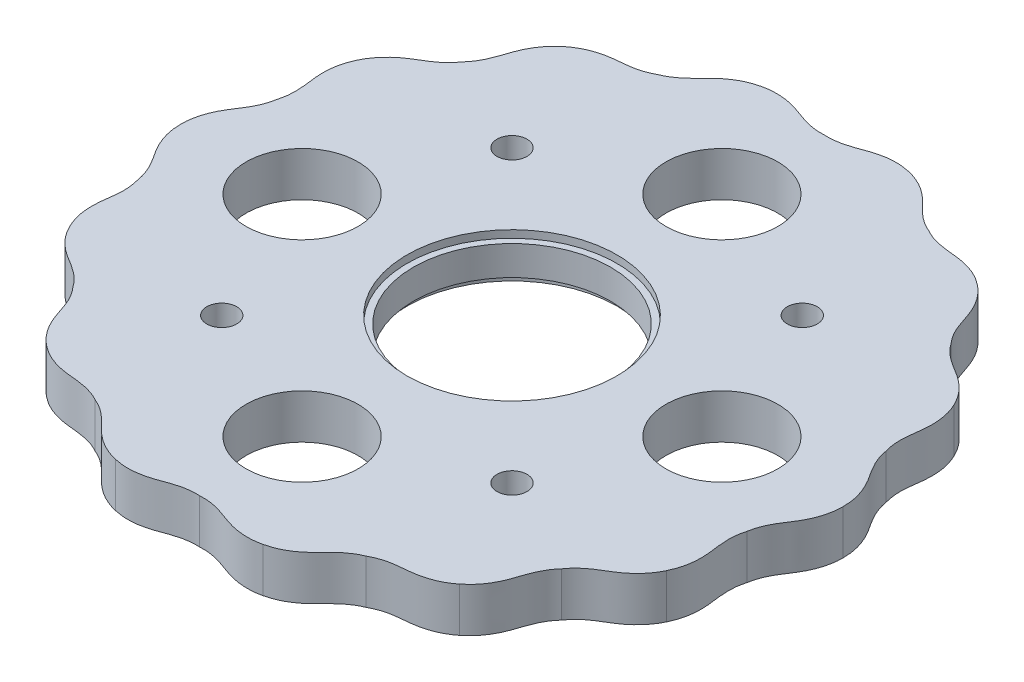
SolidWorks part; units mm, degrees
ref_plane "Front Plane" through (0, 0, 0) normal (0, 0, 1) x (1, 0, 0)
ref_plane "Top Plane" through (0, 0, 0) normal (0, 1, 0) x (1, 0, 0)
ref_plane "Right Plane" through (0, 0, 0) normal (1, 0, 0) x (0, 0, -1)
sketch "Sketch1" plane through (0, 0, 0) normal (0, 1, 0) x (1, 0, 0)
  line L0 (0, 0) -> (37.5, 0) construction
  line L1 (0, 0) -> (37.4807, 1.2019) construction
  line L2 (0, 0) -> (37.423, 2.4026) construction
  line L3 (0, 0) -> (37.3267, 3.6009) construction
  line L4 (0, 0) -> (37.1921, 4.7954) construction
  line L5 (0, 0) -> (37.0193, 5.985) construction
  line L6 (0, 0) -> (36.8085, 7.1684) construction
  line L7 (0, 0) -> (36.5598, 8.3445) construction
  line L8 (0, 0) -> (36.2736, 9.512) construction
  line L9 (0, 0) -> (35.95, 10.6698) construction
  line L10 (0, 0) -> (35.5896, 11.8166) construction
  line L11 (0, 0) -> (35.1926, 12.9512) construction
  line L12 (0, 0) -> (34.7594, 14.0725) construction
  line L13 (0, 0) -> (34.2905, 15.1794) construction
  line L14 (0, 0) -> (33.7863, 16.2706) construction
  line L15 (37.5, 0) -> (38.5, 0) construction
  line L16 (37.4807, 1.2019) -> (38.3521, 1.6927) construction
  line L17 (37.423, 2.4026) -> (37.9413, 3.2578) construction
  line L18 (37.3267, 3.6009) -> (37.3588, 4.6003) construction
  line L19 (37.1921, 4.7954) -> (36.7296, 5.682) construction
  line L20 (37.0193, 5.985) -> (36.1812, 6.5305) construction
  line L21 (36.8085, 7.1684) -> (35.8105, 7.2325) construction
  line L22 (36.5598, 8.3445) -> (35.5849, 8.122) construction
  line L23 (37, 0.0019) -> (37, 0)
  line L24 (33.3367, 16.052) -> (33.3358, 16.0537)
  line L25 (37, -0.0019) -> (37, 0)
  line L26 (33.3367, -16.052) -> (33.3358, -16.0537)
  line L27 (33.335, -16.0554) -> (33.3358, -16.0537)
  line L28 (23.0706, -28.9266) -> (23.0691, -28.9278)
  line L29 (23.0677, -28.9289) -> (23.0691, -28.9278)
  line L30 (8.2351, -36.0719) -> (8.2333, -36.0723)
  line L31 (8.2315, -36.0727) -> (8.2333, -36.0723)
  line L32 (-8.2315, -36.0727) -> (-8.2333, -36.0723)
  line L33 (-8.2351, -36.0719) -> (-8.2333, -36.0723)
  line L34 (-23.0677, -28.9289) -> (-23.0691, -28.9278)
  line L35 (-23.0706, -28.9266) -> (-23.0691, -28.9278)
  line L36 (-33.335, -16.0554) -> (-33.3358, -16.0537)
  line L37 (-33.3367, -16.052) -> (-33.3358, -16.0537)
  line L38 (-37, -0.0019) -> (-37, 0)
  line L39 (-37, 0.0019) -> (-37, 0)
  line L40 (-33.3367, 16.052) -> (-33.3358, 16.0537)
  line L41 (-33.335, 16.0554) -> (-33.3358, 16.0537)
  line L42 (-23.0706, 28.9266) -> (-23.0691, 28.9278)
  line L43 (-23.0677, 28.9289) -> (-23.0691, 28.9278)
  line L44 (-8.2351, 36.0719) -> (-8.2333, 36.0723)
  line L45 (-8.2315, 36.0727) -> (-8.2333, 36.0723)
  line L46 (8.2315, 36.0727) -> (8.2333, 36.0723)
  line L47 (8.2351, 36.0719) -> (8.2333, 36.0723)
  line L48 (23.0677, 28.9289) -> (23.0691, 28.9278)
  line L49 (23.0706, 28.9266) -> (23.0691, 28.9278)
  line L50 (33.335, 16.0554) -> (33.3358, 16.0537)
  line L51 (35.5, 0.0037) -> (35.5, 0)
  line L52 (31.986, 15.3995) -> (31.9844, 15.4029)
  line L53 (35.5, -0.0037) -> (35.5, 0)
  line L54 (31.986, -15.3995) -> (31.9844, -15.4029)
  line L55 (31.9828, -15.4062) -> (31.9844, -15.4029)
  line L56 (22.1368, -27.7527) -> (22.1339, -27.755)
  line L57 (22.131, -27.7573) -> (22.1339, -27.755)
  line L58 (7.9031, -34.6091) -> (7.8995, -34.6099)
  line L59 (7.8959, -34.6108) -> (7.8995, -34.6099)
  line L60 (-7.8959, -34.6108) -> (-7.8995, -34.6099)
  line L61 (-7.9031, -34.6091) -> (-7.8995, -34.6099)
  line L62 (-22.131, -27.7573) -> (-22.1339, -27.755)
  line L63 (-22.1368, -27.7527) -> (-22.1339, -27.755)
  line L64 (-31.9828, -15.4062) -> (-31.9844, -15.4029)
  line L65 (-31.986, -15.3995) -> (-31.9844, -15.4029)
  line L66 (-35.5, -0.0037) -> (-35.5, 0)
  line L67 (-35.5, 0.0037) -> (-35.5, 0)
  line L68 (-31.986, 15.3995) -> (-31.9844, 15.4029)
  line L69 (-31.9828, 15.4062) -> (-31.9844, 15.4029)
  line L70 (-22.1368, 27.7527) -> (-22.1339, 27.755)
  line L71 (-22.131, 27.7573) -> (-22.1339, 27.755)
  line L72 (-7.9031, 34.6091) -> (-7.8995, 34.6099)
  line L73 (-7.8959, 34.6108) -> (-7.8995, 34.6099)
  line L74 (7.8959, 34.6108) -> (7.8995, 34.6099)
  line L75 (7.9031, 34.6091) -> (7.8995, 34.6099)
  line L76 (22.131, 27.7573) -> (22.1339, 27.755)
  line L77 (22.1368, 27.7527) -> (22.1339, 27.755)
  line L78 (31.9828, 15.4062) -> (31.9844, 15.4029)
  circle A0 centre (0, 0) radius 35 construction
  circle A1 centre (37.5, 0) radius 2.5 construction
  circle A2 centre (0, 0) radius 37.5 construction
  spline S0 degree 3 poles (35.5849, 8.122) (35.6266, 7.5364) (36.0345, 6.7125) (36.7836, 5.6218) (37.4152, 4.5501) (38.2239, 2.702) (38.5014, 1.1074) (38.5, 0) knots 0 0 0 0 0.195516 0.310928 0.453873 0.621058 1 1 1 1
  spline S1 degree 3 poles (35.5849, 8.122) (35.3683, 8.6678) (35.3784, 9.5871) (35.5801, 10.8948) (35.6841, 12.1344) (35.611, 14.1503) (35.169, 15.7074) (34.6873, 16.7045) knots 0 0 0 0 0.195516 0.310928 0.453873 0.621058 1 1 1 1
  spline S2 degree 1 poles (34.1119, 7.7858) (33.3367, 16.052) knots 0 0 1 1 construction
  spline S3 degree 1 poles (34.1119, 7.7858) (37, 0.0019) knots 0 0 1 1 construction
  spline S4 degree 3 poles (33.3367, 16.052) (33.6005, 15.5058) (33.9037, 14.6401) (34.1146, 13.4372) (34.174, 12.5211) (34.1413, 11.5771) (34.0239, 10.6392) (33.8823, 9.6155) (33.9055, 8.625) (34.0243, 8.0514) (34.1119, 7.7858) knots 0.015853 0.015853 0.015853 0.015853 0.26189 0.384908 0.507927 0.630945 0.753963 0.876982 0.938491 1 1 1 1
  spline S5 degree 3 poles (34.1119, 7.7858) (34.1483, 7.5085) (34.2901, 6.9402) (34.6989, 6.0377) (35.2706, 5.1769) (35.7834, 4.3828) (36.2224, 3.5464) (36.5664, 2.6953) (36.8983, 1.52) (37.0008, 0.6085) (37, 0.0019) knots 0.015853 0.015853 0.015853 0.015853 0.077362 0.138872 0.26189 0.384908 0.507927 0.630945 0.753963 1 1 1 1
  spline S6 degree 3 poles (37, -0.0019) (37.0008, -0.6085) (36.8983, -1.52) (36.5664, -2.6953) (36.2224, -3.5464) (35.7834, -4.3828) (35.2706, -5.1769) (34.6989, -6.0377) (34.2901, -6.9402) (34.1483, -7.5085) (34.1119, -7.7858) knots 0.015853 0.015853 0.015853 0.015853 0.26189 0.384908 0.507927 0.630945 0.753963 0.876982 0.938491 1 1 1 1
  spline S7 degree 3 poles (34.1119, -7.7858) (34.0243, -8.0514) (33.9055, -8.625) (33.8823, -9.6155) (34.0239, -10.6392) (34.1413, -11.5771) (34.174, -12.5211) (34.1146, -13.4372) (33.9037, -14.6401) (33.6005, -15.5058) (33.3367, -16.052) knots 0.015853 0.015853 0.015853 0.015853 0.077362 0.138872 0.26189 0.384908 0.507927 0.630945 0.753963 1 1 1 1
  spline S8 degree 3 poles (33.335, -16.0554) (33.0725, -16.6022) (32.5847, -17.3791) (31.7758, -18.2939) (31.0965, -18.9115) (30.3381, -19.4746) (29.5316, -19.9675) (28.6429, -20.4951) (27.8831, -21.1308) (27.5087, -21.5813) (27.3556, -21.8154) knots 0.015853 0.015853 0.015853 0.015853 0.26189 0.384908 0.507927 0.630945 0.753963 0.876982 0.938491 1 1 1 1
  spline S9 degree 3 poles (27.3556, -21.8154) (27.1615, -22.0167) (26.8056, -22.4819) (26.3549, -23.3642) (26.0383, -24.348) (25.7371, -25.2439) (25.357, -26.1087) (24.906, -26.9083) (24.1941, -27.9005) (23.5453, -28.549) (23.0706, -28.9266) knots 0.015853 0.015853 0.015853 0.015853 0.077362 0.138872 0.26189 0.384908 0.507927 0.630945 0.753963 1 1 1 1
  spline S10 degree 3 poles (23.0677, -28.9289) (22.5939, -29.3077) (21.8173, -29.796) (20.6915, -30.2693) (19.8116, -30.531) (18.884, -30.7092) (17.9435, -30.8034) (16.9139, -30.8931) (15.9535, -31.1362) (15.4207, -31.3797) (15.1812, -31.5241) knots 0.015853 0.015853 0.015853 0.015853 0.26189 0.384908 0.507927 0.630945 0.753963 0.876982 0.938491 1 1 1 1
  spline S11 degree 3 poles (15.1812, -31.5241) (14.919, -31.6213) (14.3964, -31.886) (13.6076, -32.4854) (12.8955, -33.2344) (12.2354, -33.9109) (11.5177, -34.5251) (10.7645, -35.0499) (9.6926, -35.6349) (8.8266, -35.9377) (8.2351, -36.0719) knots 0.015853 0.015853 0.015853 0.015853 0.077362 0.138872 0.26189 0.384908 0.507927 0.630945 0.753963 1 1 1 1
  spline S12 degree 3 poles (8.2315, -36.0727) (7.6402, -36.2085) (6.7287, -36.3114) (5.5091, -36.2494) (4.6028, -36.1034) (3.6897, -35.8614) (2.8014, -35.5383) (1.8349, -35.1724) (0.8641, -34.9747) (0.2785, -34.9629) (0, -34.9891) knots 0.015853 0.015853 0.015853 0.015853 0.26189 0.384908 0.507927 0.630945 0.753963 0.876982 0.938491 1 1 1 1
  spline S13 degree 3 poles (0, -34.9891) (-0.2785, -34.9629) (-0.8641, -34.9747) (-1.8349, -35.1724) (-2.8014, -35.5383) (-3.6897, -35.8614) (-4.6028, -36.1034) (-5.5091, -36.2494) (-6.7287, -36.3114) (-7.6402, -36.2085) (-8.2315, -36.0727) knots 0.015853 0.015853 0.015853 0.015853 0.077362 0.138872 0.26189 0.384908 0.507927 0.630945 0.753963 1 1 1 1
  spline S14 degree 3 poles (-8.2351, -36.0719) (-8.8266, -35.9377) (-9.6926, -35.6349) (-10.7645, -35.0499) (-11.5177, -34.5251) (-12.2354, -33.9109) (-12.8955, -33.2344) (-13.6076, -32.4854) (-14.3964, -31.886) (-14.919, -31.6213) (-15.1812, -31.5241) knots 0.015853 0.015853 0.015853 0.015853 0.26189 0.384908 0.507927 0.630945 0.753963 0.876982 0.938491 1 1 1 1
  spline S15 degree 3 poles (-15.1812, -31.5241) (-15.4207, -31.3797) (-15.9535, -31.1362) (-16.9139, -30.8931) (-17.9435, -30.8034) (-18.884, -30.7092) (-19.8116, -30.531) (-20.6915, -30.2693) (-21.8173, -29.796) (-22.5939, -29.3077) (-23.0677, -28.9289) knots 0.015853 0.015853 0.015853 0.015853 0.077362 0.138872 0.26189 0.384908 0.507927 0.630945 0.753963 1 1 1 1
  spline S16 degree 3 poles (-23.0706, -28.9266) (-23.5453, -28.549) (-24.1941, -27.9005) (-24.906, -26.9083) (-25.357, -26.1087) (-25.7371, -25.2439) (-26.0383, -24.348) (-26.3549, -23.3642) (-26.8056, -22.4819) (-27.1615, -22.0167) (-27.3556, -21.8154) knots 0.015853 0.015853 0.015853 0.015853 0.26189 0.384908 0.507927 0.630945 0.753963 0.876982 0.938491 1 1 1 1
  spline S17 degree 3 poles (-27.3556, -21.8154) (-27.5087, -21.5813) (-27.8831, -21.1308) (-28.6429, -20.4951) (-29.5316, -19.9675) (-30.3381, -19.4746) (-31.0965, -18.9115) (-31.7758, -18.2939) (-32.5847, -17.3791) (-33.0725, -16.6022) (-33.335, -16.0554) knots 0.015853 0.015853 0.015853 0.015853 0.077362 0.138872 0.26189 0.384908 0.507927 0.630945 0.753963 1 1 1 1
  spline S18 degree 3 poles (-33.3367, -16.052) (-33.6005, -15.5058) (-33.9037, -14.6401) (-34.1146, -13.4372) (-34.174, -12.5211) (-34.1413, -11.5771) (-34.0239, -10.6392) (-33.8823, -9.6155) (-33.9055, -8.625) (-34.0243, -8.0514) (-34.1119, -7.7858) knots 0.015853 0.015853 0.015853 0.015853 0.26189 0.384908 0.507927 0.630945 0.753963 0.876982 0.938491 1 1 1 1
  spline S19 degree 3 poles (-34.1119, -7.7858) (-34.1483, -7.5085) (-34.2901, -6.9402) (-34.6989, -6.0377) (-35.2706, -5.1769) (-35.7834, -4.3828) (-36.2224, -3.5464) (-36.5664, -2.6953) (-36.8983, -1.52) (-37.0008, -0.6085) (-37, -0.0019) knots 0.015853 0.015853 0.015853 0.015853 0.077362 0.138872 0.26189 0.384908 0.507927 0.630945 0.753963 1 1 1 1
  spline S20 degree 3 poles (-37, 0.0019) (-37.0008, 0.6085) (-36.8983, 1.52) (-36.5664, 2.6953) (-36.2224, 3.5464) (-35.7834, 4.3828) (-35.2706, 5.1769) (-34.6989, 6.0377) (-34.2901, 6.9402) (-34.1483, 7.5085) (-34.1119, 7.7858) knots 0.015853 0.015853 0.015853 0.015853 0.26189 0.384908 0.507927 0.630945 0.753963 0.876982 0.938491 1 1 1 1
  spline S21 degree 3 poles (-34.1119, 7.7858) (-34.0243, 8.0514) (-33.9055, 8.625) (-33.8823, 9.6155) (-34.0239, 10.6392) (-34.1413, 11.5771) (-34.174, 12.5211) (-34.1146, 13.4372) (-33.9037, 14.6401) (-33.6005, 15.5058) (-33.3367, 16.052) knots 0.015853 0.015853 0.015853 0.015853 0.077362 0.138872 0.26189 0.384908 0.507927 0.630945 0.753963 1 1 1 1
  spline S22 degree 3 poles (-33.335, 16.0554) (-33.0725, 16.6022) (-32.5847, 17.3791) (-31.7758, 18.2939) (-31.0965, 18.9115) (-30.3381, 19.4746) (-29.5316, 19.9675) (-28.6429, 20.4951) (-27.8831, 21.1308) (-27.5087, 21.5813) (-27.3556, 21.8154) knots 0.015853 0.015853 0.015853 0.015853 0.26189 0.384908 0.507927 0.630945 0.753963 0.876982 0.938491 1 1 1 1
  spline S23 degree 3 poles (-27.3556, 21.8154) (-27.1615, 22.0167) (-26.8056, 22.4819) (-26.3549, 23.3642) (-26.0383, 24.348) (-25.7371, 25.2439) (-25.357, 26.1087) (-24.906, 26.9083) (-24.1941, 27.9005) (-23.5453, 28.549) (-23.0706, 28.9266) knots 0.015853 0.015853 0.015853 0.015853 0.077362 0.138872 0.26189 0.384908 0.507927 0.630945 0.753963 1 1 1 1
  spline S24 degree 3 poles (-23.0677, 28.9289) (-22.5939, 29.3077) (-21.8173, 29.796) (-20.6915, 30.2693) (-19.8116, 30.531) (-18.884, 30.7092) (-17.9435, 30.8034) (-16.9139, 30.8931) (-15.9535, 31.1362) (-15.4207, 31.3797) (-15.1812, 31.5241) knots 0.015853 0.015853 0.015853 0.015853 0.26189 0.384908 0.507927 0.630945 0.753963 0.876982 0.938491 1 1 1 1
  spline S25 degree 3 poles (-15.1812, 31.5241) (-14.919, 31.6213) (-14.3964, 31.886) (-13.6076, 32.4854) (-12.8955, 33.2344) (-12.2354, 33.9109) (-11.5177, 34.5251) (-10.7645, 35.0499) (-9.6926, 35.6349) (-8.8266, 35.9377) (-8.2351, 36.0719) knots 0.015853 0.015853 0.015853 0.015853 0.077362 0.138872 0.26189 0.384908 0.507927 0.630945 0.753963 1 1 1 1
  spline S26 degree 3 poles (-8.2315, 36.0727) (-7.6402, 36.2085) (-6.7287, 36.3114) (-5.5091, 36.2494) (-4.6028, 36.1034) (-3.6897, 35.8614) (-2.8014, 35.5383) (-1.8349, 35.1724) (-0.8641, 34.9747) (-0.2785, 34.9629) (0, 34.9891) knots 0.015853 0.015853 0.015853 0.015853 0.26189 0.384908 0.507927 0.630945 0.753963 0.876982 0.938491 1 1 1 1
  spline S27 degree 3 poles (0, 34.9891) (0.2785, 34.9629) (0.8641, 34.9747) (1.8349, 35.1724) (2.8014, 35.5383) (3.6897, 35.8614) (4.6028, 36.1034) (5.5091, 36.2494) (6.7287, 36.3114) (7.6402, 36.2085) (8.2315, 36.0727) knots 0.015853 0.015853 0.015853 0.015853 0.077362 0.138872 0.26189 0.384908 0.507927 0.630945 0.753963 1 1 1 1
  spline S28 degree 3 poles (8.2351, 36.0719) (8.8266, 35.9377) (9.6926, 35.6349) (10.7645, 35.0499) (11.5177, 34.5251) (12.2354, 33.9109) (12.8955, 33.2344) (13.6076, 32.4854) (14.3964, 31.886) (14.919, 31.6213) (15.1812, 31.5241) knots 0.015853 0.015853 0.015853 0.015853 0.26189 0.384908 0.507927 0.630945 0.753963 0.876982 0.938491 1 1 1 1
  spline S29 degree 3 poles (15.1812, 31.5241) (15.4207, 31.3797) (15.9535, 31.1362) (16.9139, 30.8931) (17.9435, 30.8034) (18.884, 30.7092) (19.8116, 30.531) (20.6915, 30.2693) (21.8173, 29.796) (22.5939, 29.3077) (23.0677, 28.9289) knots 0.015853 0.015853 0.015853 0.015853 0.077362 0.138872 0.26189 0.384908 0.507927 0.630945 0.753963 1 1 1 1
  spline S30 degree 3 poles (23.0706, 28.9266) (23.5453, 28.549) (24.1941, 27.9005) (24.906, 26.9083) (25.357, 26.1087) (25.7371, 25.2439) (26.0383, 24.348) (26.3549, 23.3642) (26.8056, 22.4819) (27.1615, 22.0167) (27.3556, 21.8154) knots 0.015853 0.015853 0.015853 0.015853 0.26189 0.384908 0.507927 0.630945 0.753963 0.876982 0.938491 1 1 1 1
  spline S31 degree 3 poles (27.3556, 21.8154) (27.5087, 21.5813) (27.8831, 21.1308) (28.6429, 20.4951) (29.5316, 19.9675) (30.3381, 19.4746) (31.0965, 18.9115) (31.7758, 18.2939) (32.5847, 17.3791) (33.0725, 16.6022) (33.335, 16.0554) knots 0.015853 0.015853 0.015853 0.015853 0.077362 0.138872 0.26189 0.384908 0.507927 0.630945 0.753963 1 1 1 1
  spline S32 degree 1 poles (32.6448, 7.451) (35.5, 0.0037) knots 0 0 1 1 construction
  spline S33 degree 1 poles (32.6448, 7.451) (31.986, 15.3995) knots 0 0 1 1 construction
  spline S34 degree 3 poles (35.5, 0.0037) (35.5006, 0.4959) (35.4183, 1.2336) (35.1496, 2.1927) (34.8707, 2.8896) (34.4997, 3.6015) (34.1394, 4.1652) (33.6939, 4.8394) (33.3068, 5.4873) (32.9751, 6.1975) (32.758, 6.8733) (32.6748, 7.2607) (32.6448, 7.451) knots 0.023011 0.023011 0.023011 0.023011 0.267258 0.389382 0.511505 0.633629 0.755753 0.816814 0.877876 0.938938 0.969469 1 1 1 1
  spline S35 degree 3 poles (32.6448, 7.451) (32.5893, 7.6354) (32.4961, 8.0206) (32.3985, 8.7236) (32.3893, 9.5074) (32.4569, 10.2591) (32.5657, 11.0598) (32.6458, 11.724) (32.6712, 12.5264) (32.6201, 13.2752) (32.446, 14.256) (32.2001, 14.9563) (31.986, 15.3995) knots 0.023011 0.023011 0.023011 0.023011 0.053542 0.084072 0.145134 0.206196 0.267258 0.389382 0.511505 0.633629 0.755753 1 1 1 1
  spline S36 degree 3 poles (32.6448, -7.451) (32.6748, -7.2607) (32.758, -6.8733) (32.9751, -6.1975) (33.3068, -5.4873) (33.6939, -4.8394) (34.1394, -4.1652) (34.4997, -3.6015) (34.8707, -2.8896) (35.1496, -2.1927) (35.4183, -1.2336) (35.5006, -0.4959) (35.5, -0.0037) knots 0.023011 0.023011 0.023011 0.023011 0.053542 0.084072 0.145134 0.206196 0.267258 0.389382 0.511505 0.633629 0.755753 1 1 1 1
  spline S37 degree 3 poles (31.986, -15.3995) (32.2001, -14.9563) (32.446, -14.256) (32.6201, -13.2752) (32.6712, -12.5264) (32.6458, -11.724) (32.5657, -11.0598) (32.4569, -10.2591) (32.3893, -9.5074) (32.3985, -8.7236) (32.4961, -8.0206) (32.5893, -7.6354) (32.6448, -7.451) knots 0.023011 0.023011 0.023011 0.023011 0.267258 0.389382 0.511505 0.633629 0.755753 0.816814 0.877876 0.938938 0.969469 1 1 1 1
  spline S38 degree 3 poles (26.1791, -20.8771) (26.2887, -20.7187) (26.5317, -20.4057) (27.0205, -19.8911) (27.6275, -19.3952) (28.2574, -18.9793) (28.9513, -18.5652) (29.5206, -18.2137) (30.1637, -17.7333) (30.7173, -17.2264) (31.3755, -16.4789) (31.7698, -15.8499) (31.9828, -15.4062) knots 0.023011 0.023011 0.023011 0.023011 0.053542 0.084072 0.145134 0.206196 0.267258 0.389382 0.511505 0.633629 0.755753 1 1 1 1
  spline S39 degree 3 poles (22.1368, -27.7527) (22.522, -27.4463) (23.0474, -26.922) (23.6297, -26.1139) (24.0007, -25.4614) (24.326, -24.7275) (24.542, -24.0943) (24.7914, -23.3257) (25.0566, -22.619) (25.405, -21.9169) (25.798, -21.3258) (26.0491, -21.0192) (26.1791, -20.8771) knots 0.023011 0.023011 0.023011 0.023011 0.267258 0.389382 0.511505 0.633629 0.755753 0.816814 0.877876 0.938938 0.969469 1 1 1 1
  spline S40 degree 3 poles (14.5283, -30.1683) (14.6957, -30.0732) (15.0505, -29.8966) (15.7143, -29.645) (16.4763, -29.4616) (17.2242, -29.3602) (18.0291, -29.2882) (18.6945, -29.2185) (19.4823, -29.0647) (20.201, -28.8482) (21.1184, -28.4603) (21.7465, -28.0647) (22.131, -27.7573) knots 0.023011 0.023011 0.023011 0.023011 0.053542 0.084072 0.145134 0.206196 0.267258 0.389382 0.511505 0.633629 0.755753 1 1 1 1
  spline S41 degree 3 poles (7.9031, -34.6091) (8.3831, -34.5002) (9.084, -34.2557) (9.9593, -33.7804) (10.5766, -33.3534) (11.1881, -32.8334) (11.6575, -32.3566) (12.2156, -31.7723) (12.7612, -31.2507) (13.3797, -30.7693) (13.9903, -30.4072) (14.3495, -30.2399) (14.5283, -30.1683) knots 0.023011 0.023011 0.023011 0.023011 0.267258 0.389382 0.511505 0.633629 0.755753 0.816814 0.877876 0.938938 0.969469 1 1 1 1
  spline S42 degree 3 poles (0, -33.4843) (0.1922, -33.4712) (0.5884, -33.4661) (1.2956, -33.5274) (2.0617, -33.6928) (2.7796, -33.926) (3.536, -34.2103) (4.1657, -34.4362) (4.9423, -34.6394) (5.6838, -34.7562) (6.6786, -34.8048) (7.4161, -34.7209) (7.8959, -34.6108) knots 0.023011 0.023011 0.023011 0.023011 0.053542 0.084072 0.145134 0.206196 0.267258 0.389382 0.511505 0.633629 0.755753 1 1 1 1
  spline S43 degree 3 poles (-7.8959, -34.6108) (-7.4161, -34.7209) (-6.6786, -34.8048) (-5.6838, -34.7562) (-4.9423, -34.6394) (-4.1657, -34.4362) (-3.536, -34.2103) (-2.7796, -33.926) (-2.0617, -33.6928) (-1.2956, -33.5274) (-0.5884, -33.4661) (-0.1922, -33.4712) (0, -33.4843) knots 0.023011 0.023011 0.023011 0.023011 0.267258 0.389382 0.511505 0.633629 0.755753 0.816814 0.877876 0.938938 0.969469 1 1 1 1
  spline S44 degree 3 poles (-14.5283, -30.1683) (-14.3495, -30.2399) (-13.9903, -30.4072) (-13.3797, -30.7693) (-12.7612, -31.2507) (-12.2156, -31.7723) (-11.6575, -32.3566) (-11.1881, -32.8334) (-10.5766, -33.3534) (-9.9593, -33.7804) (-9.084, -34.2557) (-8.3831, -34.5002) (-7.9031, -34.6091) knots 0.023011 0.023011 0.023011 0.023011 0.053542 0.084072 0.145134 0.206196 0.267258 0.389382 0.511505 0.633629 0.755753 1 1 1 1
  spline S45 degree 3 poles (-22.131, -27.7573) (-21.7465, -28.0647) (-21.1184, -28.4603) (-20.201, -28.8482) (-19.4823, -29.0647) (-18.6945, -29.2185) (-18.0291, -29.2882) (-17.2242, -29.3602) (-16.4763, -29.4616) (-15.7143, -29.645) (-15.0505, -29.8966) (-14.6957, -30.0732) (-14.5283, -30.1683) knots 0.023011 0.023011 0.023011 0.023011 0.267258 0.389382 0.511505 0.633629 0.755753 0.816814 0.877876 0.938938 0.969469 1 1 1 1
  spline S46 degree 3 poles (-26.1791, -20.8771) (-26.0491, -21.0192) (-25.798, -21.3258) (-25.405, -21.9169) (-25.0566, -22.619) (-24.7914, -23.3257) (-24.542, -24.0943) (-24.326, -24.7275) (-24.0007, -25.4614) (-23.6297, -26.1139) (-23.0474, -26.922) (-22.522, -27.4463) (-22.1368, -27.7527) knots 0.023011 0.023011 0.023011 0.023011 0.053542 0.084072 0.145134 0.206196 0.267258 0.389382 0.511505 0.633629 0.755753 1 1 1 1
  spline S47 degree 3 poles (-31.9828, -15.4062) (-31.7698, -15.8499) (-31.3755, -16.4789) (-30.7173, -17.2264) (-30.1637, -17.7333) (-29.5206, -18.2137) (-28.9513, -18.5652) (-28.2574, -18.9793) (-27.6275, -19.3952) (-27.0205, -19.8911) (-26.5317, -20.4057) (-26.2887, -20.7187) (-26.1791, -20.8771) knots 0.023011 0.023011 0.023011 0.023011 0.267258 0.389382 0.511505 0.633629 0.755753 0.816814 0.877876 0.938938 0.969469 1 1 1 1
  spline S48 degree 3 poles (-32.6448, -7.451) (-32.5893, -7.6354) (-32.4961, -8.0206) (-32.3985, -8.7236) (-32.3893, -9.5074) (-32.4569, -10.2591) (-32.5657, -11.0598) (-32.6458, -11.724) (-32.6712, -12.5264) (-32.6201, -13.2752) (-32.446, -14.256) (-32.2001, -14.9563) (-31.986, -15.3995) knots 0.023011 0.023011 0.023011 0.023011 0.053542 0.084072 0.145134 0.206196 0.267258 0.389382 0.511505 0.633629 0.755753 1 1 1 1
  spline S49 degree 3 poles (-35.5, -0.0037) (-35.5006, -0.4959) (-35.4183, -1.2336) (-35.1496, -2.1927) (-34.8707, -2.8896) (-34.4997, -3.6015) (-34.1394, -4.1652) (-33.6939, -4.8394) (-33.3068, -5.4873) (-32.9751, -6.1975) (-32.758, -6.8733) (-32.6748, -7.2607) (-32.6448, -7.451) knots 0.023011 0.023011 0.023011 0.023011 0.267258 0.389382 0.511505 0.633629 0.755753 0.816814 0.877876 0.938938 0.969469 1 1 1 1
  spline S50 degree 3 poles (-32.6448, 7.451) (-32.6748, 7.2607) (-32.758, 6.8733) (-32.9751, 6.1975) (-33.3068, 5.4873) (-33.6939, 4.8394) (-34.1394, 4.1652) (-34.4997, 3.6015) (-34.8707, 2.8896) (-35.1496, 2.1927) (-35.4183, 1.2336) (-35.5006, 0.4959) (-35.5, 0.0037) knots 0.023011 0.023011 0.023011 0.023011 0.053542 0.084072 0.145134 0.206196 0.267258 0.389382 0.511505 0.633629 0.755753 1 1 1 1
  spline S51 degree 3 poles (-31.986, 15.3995) (-32.2001, 14.9563) (-32.446, 14.256) (-32.6201, 13.2752) (-32.6712, 12.5264) (-32.6458, 11.724) (-32.5657, 11.0598) (-32.4569, 10.2591) (-32.3893, 9.5074) (-32.3985, 8.7236) (-32.4961, 8.0206) (-32.5893, 7.6354) (-32.6448, 7.451) knots 0.023011 0.023011 0.023011 0.023011 0.267258 0.389382 0.511505 0.633629 0.755753 0.816814 0.877876 0.938938 0.969469 1 1 1 1
  spline S52 degree 3 poles (-26.1791, 20.8771) (-26.2887, 20.7187) (-26.5317, 20.4057) (-27.0205, 19.8911) (-27.6275, 19.3952) (-28.2574, 18.9793) (-28.9513, 18.5652) (-29.5206, 18.2137) (-30.1637, 17.7333) (-30.7173, 17.2264) (-31.3755, 16.4789) (-31.7698, 15.8499) (-31.9828, 15.4062) knots 0.023011 0.023011 0.023011 0.023011 0.053542 0.084072 0.145134 0.206196 0.267258 0.389382 0.511505 0.633629 0.755753 1 1 1 1
  spline S53 degree 3 poles (-22.1368, 27.7527) (-22.522, 27.4463) (-23.0474, 26.922) (-23.6297, 26.1139) (-24.0007, 25.4614) (-24.326, 24.7275) (-24.542, 24.0943) (-24.7914, 23.3257) (-25.0566, 22.619) (-25.405, 21.9169) (-25.798, 21.3258) (-26.0491, 21.0192) (-26.1791, 20.8771) knots 0.023011 0.023011 0.023011 0.023011 0.267258 0.389382 0.511505 0.633629 0.755753 0.816814 0.877876 0.938938 0.969469 1 1 1 1
  spline S54 degree 3 poles (-14.5283, 30.1683) (-14.6957, 30.0732) (-15.0505, 29.8966) (-15.7143, 29.645) (-16.4763, 29.4616) (-17.2242, 29.3602) (-18.0291, 29.2882) (-18.6945, 29.2185) (-19.4823, 29.0647) (-20.201, 28.8482) (-21.1184, 28.4603) (-21.7465, 28.0647) (-22.131, 27.7573) knots 0.023011 0.023011 0.023011 0.023011 0.053542 0.084072 0.145134 0.206196 0.267258 0.389382 0.511505 0.633629 0.755753 1 1 1 1
  spline S55 degree 3 poles (-7.9031, 34.6091) (-8.3831, 34.5002) (-9.084, 34.2557) (-9.9593, 33.7804) (-10.5766, 33.3534) (-11.1881, 32.8334) (-11.6575, 32.3566) (-12.2156, 31.7723) (-12.7612, 31.2507) (-13.3797, 30.7693) (-13.9903, 30.4072) (-14.3495, 30.2399) (-14.5283, 30.1683) knots 0.023011 0.023011 0.023011 0.023011 0.267258 0.389382 0.511505 0.633629 0.755753 0.816814 0.877876 0.938938 0.969469 1 1 1 1
  spline S56 degree 3 poles (0, 33.4843) (-0.1922, 33.4712) (-0.5884, 33.4661) (-1.2956, 33.5274) (-2.0617, 33.6928) (-2.7796, 33.926) (-3.536, 34.2103) (-4.1657, 34.4362) (-4.9423, 34.6394) (-5.6838, 34.7562) (-6.6786, 34.8048) (-7.4161, 34.7209) (-7.8959, 34.6108) knots 0.023011 0.023011 0.023011 0.023011 0.053542 0.084072 0.145134 0.206196 0.267258 0.389382 0.511505 0.633629 0.755753 1 1 1 1
  spline S57 degree 3 poles (7.8959, 34.6108) (7.4161, 34.7209) (6.6786, 34.8048) (5.6838, 34.7562) (4.9423, 34.6394) (4.1657, 34.4362) (3.536, 34.2103) (2.7796, 33.926) (2.0617, 33.6928) (1.2956, 33.5274) (0.5884, 33.4661) (0.1922, 33.4712) (0, 33.4843) knots 0.023011 0.023011 0.023011 0.023011 0.267258 0.389382 0.511505 0.633629 0.755753 0.816814 0.877876 0.938938 0.969469 1 1 1 1
  spline S58 degree 3 poles (14.5283, 30.1683) (14.3495, 30.2399) (13.9903, 30.4072) (13.3797, 30.7693) (12.7612, 31.2507) (12.2156, 31.7723) (11.6575, 32.3566) (11.1881, 32.8334) (10.5766, 33.3534) (9.9593, 33.7804) (9.084, 34.2557) (8.3831, 34.5002) (7.9031, 34.6091) knots 0.023011 0.023011 0.023011 0.023011 0.053542 0.084072 0.145134 0.206196 0.267258 0.389382 0.511505 0.633629 0.755753 1 1 1 1
  spline S59 degree 3 poles (22.131, 27.7573) (21.7465, 28.0647) (21.1184, 28.4603) (20.201, 28.8482) (19.4823, 29.0647) (18.6945, 29.2185) (18.0291, 29.2882) (17.2242, 29.3602) (16.4763, 29.4616) (15.7143, 29.645) (15.0505, 29.8966) (14.6957, 30.0732) (14.5283, 30.1683) knots 0.023011 0.023011 0.023011 0.023011 0.267258 0.389382 0.511505 0.633629 0.755753 0.816814 0.877876 0.938938 0.969469 1 1 1 1
  spline S60 degree 3 poles (26.1791, 20.8771) (26.0491, 21.0192) (25.798, 21.3258) (25.405, 21.9169) (25.0566, 22.619) (24.7914, 23.3257) (24.542, 24.0943) (24.326, 24.7275) (24.0007, 25.4614) (23.6297, 26.1139) (23.0474, 26.922) (22.522, 27.4463) (22.1368, 27.7527) knots 0.023011 0.023011 0.023011 0.023011 0.053542 0.084072 0.145134 0.206196 0.267258 0.389382 0.511505 0.633629 0.755753 1 1 1 1
  spline S61 degree 3 poles (31.9828, 15.4062) (31.7698, 15.8499) (31.3755, 16.4789) (30.7173, 17.2264) (30.1637, 17.7333) (29.5206, 18.2137) (28.9513, 18.5652) (28.2574, 18.9793) (27.6275, 19.3952) (27.0205, 19.8911) (26.5317, 20.4057) (26.2887, 20.7187) (26.1791, 20.8771) knots 0.023011 0.023011 0.023011 0.023011 0.267258 0.389382 0.511505 0.633629 0.755753 0.816814 0.877876 0.938938 0.969469 1 1 1 1
  point P25 (0, 0)
  point P117 (0, 0)
  point P174 (0, 0)
  dimension "D1" = 70
  dimension "D2" = 5
  dimension "D4" = 25.714
  dimension "D5" = 1
  dimension "D7" = 180
  dimension "D8" = 207.551
  dimension "D6" = 1
  dimension "D9" = 1
  dimension "D10" = 235.102
  dimension "D11" = 1
  dimension "D12" = 1
  dimension "D13" = 1
  dimension "D14" = 1
  dimension "D15" = 1
  dimension "D16" = 262.653
  dimension "D17" = 290.204
  dimension "D18" = 317.755
  dimension "D19" = 345.306
  dimension "D20" = 1.5
  dimension "D22" = 3
  dimension "D3" = 15
  dimension "D21" = 14
  dimension "D23" = 14
extrude "Boss-Extrude3" add sketch "Sketch1" along normal blind 4.7625 contours L51 L53 S36 S37 L54 L55 S38 S39 L56 L57 S40 S41 L58 L59 S42 S43 L60 L61 S44 S45 L62 L63 S46 S47 L64 L65 S48 S49 L66 L67 S50 S51 L68 L69 S52 S53 L70 L71 S54 S55 L72 L73 S56 S57 L74 L75 S58 S59 L76 L77 S60 S61 L78 L52 S35 S34
sketch "Sketch2" plane through (0, 4.7625, 0) normal (0, 1, 0) x (1, 0, 0)
  line L0 (0, 0) -> (22.5, 0) construction
  line L1 (0, 0) -> (15.5563, 15.5563) construction
  circle A0 centre (0, 0) radius 10.5635
  circle A1 centre (22.5, 0) radius 6
  circle A6 centre (15.5563, 15.5563) radius 1.607
  circle A7 centre (0, -22.5) radius 6
  circle A8 centre (15.5563, -15.5563) radius 1.607
  circle A9 centre (-22.5, 0) radius 6
  circle A10 centre (-15.5563, -15.5563) radius 1.607
  circle A11 centre (0, 22.5) radius 6
  circle A12 centre (-15.5563, 15.5563) radius 1.607
  point P16 (0, 0)
  point P21 (0, 0)
  point P24 (0, 0)
  dimension "D3" = 12
  dimension "D1" = 21.127
  dimension "D6" = 3.214
  dimension "D2" = 22.5
  dimension "D4" = 45
  dimension "D5" = 22
  dimension "D7" = 4
extrude "Cut-Extrude1" cut sketch "Sketch2" against normal blind 4.7625 contours A7 | A0 | A0 | A0 | L0 A0 | A0 L0 | A1 | A9 | A11 region at (0, 4.7625, 0) region at (22.5, 4.7625, 0) region at (0, 4.7625, 22.5) region at (-22.5, 4.7625, 0) region at (0, 4.7625, -22.5)
extrude "Cut-Extrude2" cut sketch "Sketch2<4>" against normal blind 2.4105 contours A12 | A10 | A8 | A6 region at (15.5563, 4.7625, -15.5563) region at (15.5563, 4.7625, 15.5563) region at (-15.5563, 4.7625, 15.5563) region at (-15.5563, 4.7625, -15.5563)
sketch "Sketch2<4>" plane through (0, 4.7625, 0) normal (0, 1, 0) x (1, 0, 0) same geometry as "Sketch2"
sketch "Sketch3" plane through (0, 4.7625, 0) normal (0, 1, 0) x (1, 0, 0)
  circle A0 centre (0, 0) radius 11.25
  dimension "D1" = 22.5
extrude "Cut-Extrude3" cut sketch "Sketch3" against normal blind 0.8
extrude "Cut-Extrude4" cut sketch "Sketch3<2>" along normal blind 0.8 from surface starting at face at (0, 0, 28.5)
sketch "Sketch3<2>" plane through (0, 4.7625, 0) normal (0, 1, 0) x (1, 0, 0) same geometry as "Sketch3"
equation "\"D5@Sketch1\" = \"eccentricity\""
equation "\"D6@Sketch1\" = \"eccentricity\""
equation "\"D9@Sketch1\" = \"eccentricity\""
equation "\"D11@Sketch1\" = \"eccentricity\""
equation "\"D12@Sketch1\" = \"eccentricity\""
equation "\"D14@Sketch1\" = \"eccentricity\""
equation "\"D13@Sketch1\" = \"eccentricity\""
equation "\"D15@Sketch1\"= \"eccentricity\""
equation "\"D1@Sketch2\"=\"largeBearOD\"+\"largeBearOTight\""
equation "\"D1@Cut-Extrude2\"=\"ballBearDiam\" * 0.75"
equation "\"D1@Boss-Extrude3\"=\"sheetThickness\""
equation "\"smallBearOD\"= 15mm"
equation "\"smallBearID\" = 0mm"
equation "\"smallBearOTight\"= 0mm'calibrate - hold onto bottom of gearbox"
equation "\"smallBearOLoose\"= 0mm'calibrate - able to take off topHat"
equation "\"smallBearITight\" = 0mm'hold onto "
equation "\"pinCircleDiam\"= 75mm"
equation "\"pinDiam\"= 6mm"
equation "\"sheetThickness\"= 0.1875in"
equation "\"D6@Sketch2\"=\"ballBearDiam\""
equation "\"largeBearOD\"= 21mm"
equation "\"largeBearID\" = 15mm"
equation "\"largeBearOTight\"= 0.127mm'calibrate - hold onto gears"
equation "\"largeBearITight\"= 0mm'calibrate - hold onto eccentric nut"
equation "\"ballBearDiam\"= 3.214mm"
equation "\"thrustBearingThickness\"= 5mm'measure this irl and change"
equation "\"thrustBearingID\"= 0mm'measure this irl and change"
equation "\"thrustBearingOD\"= 0mm'measure this irl and change"
equation "\"eccentricity\" = 1mm"
equation "\"D1@Cut-Extrude1\"=\"sheetThickness\""
